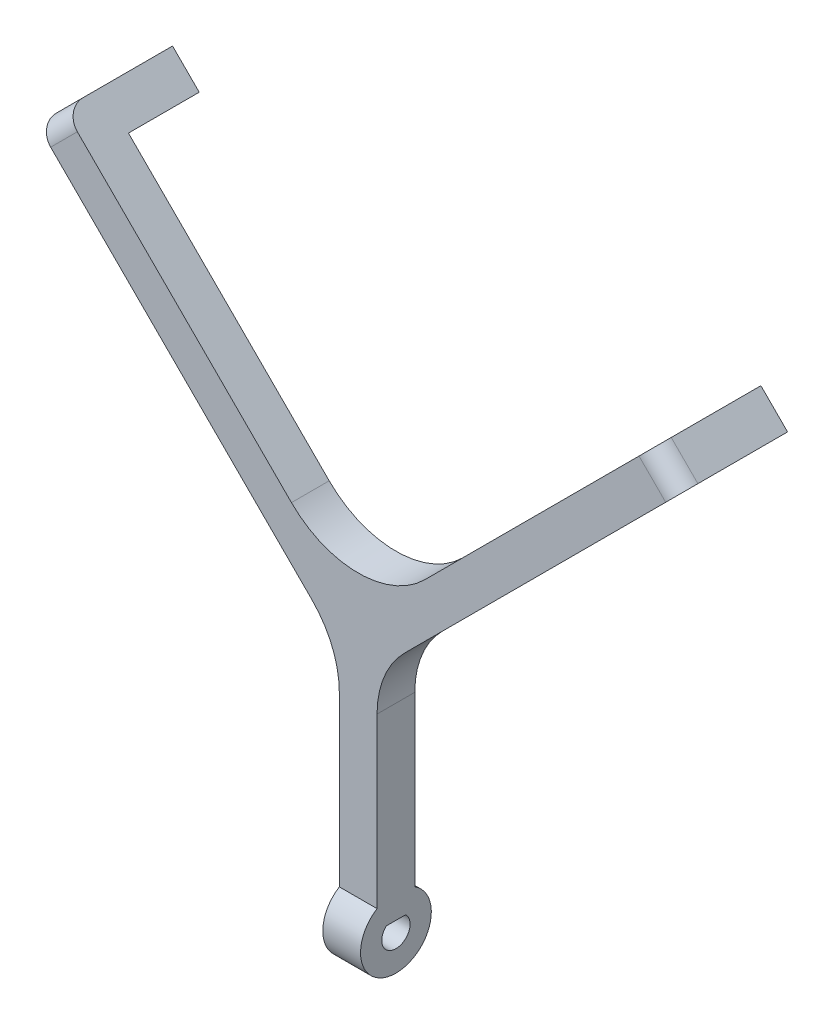
SolidWorks part; units mm, degrees
material "PLA"
ref_plane "Plan de face" through (0, 0, 0) normal (0, 0, 1) x (1, 0, 0)
ref_plane "Plan de dessus" through (0, 0, 0) normal (0, 1, 0) x (1, 0, 0)
ref_plane "Plan de droite" through (0, 0, 0) normal (1, 0, 0) x (0, 0, -1)
sketch "Esquisse1" plane through (0, 0, 0) normal (0, 0, 1) x (1, 0, 0)
  line L1 (0, 0) -> (136, 0) construction
  line L2 (0, 0) -> (0, 120) construction
  line L3 (0, 120) -> (136, 120) construction
  line L4 (136, 0) -> (136, 120) construction
  line L16 (64, 0) -> (64, 50.3431)
  line L17 (64, 50.3431) -> (0, 114.3431)
  line L18 (0, 114.3431) -> (5.6569, 120)
  line L19 (5.6569, 120) -> (68, 57.6569)
  line L20 (68, 57.6569) -> (130.3431, 120)
  line L21 (130.3431, 120) -> (136, 114.3431)
  line L22 (136, 114.3431) -> (72, 50.3431)
  line L23 (72, 50.3431) -> (72, 0)
  line L24 (72, 0) -> (64, 0)
  point P19 (68, 0)
  dimension "D1" = 136
  dimension "D2" = 120
  dimension "D3" = 8
  dimension "D4" = 68
  dimension "D5" = 135
  dimension "D6" = 135
  dimension "D7" = 90
  dimension "D8" = 8
  dimension "D9" = 8
  dimension "D10" = 68
extrude "Boss.-Extru.1" add sketch "Esquisse1" along normal blind 8
sketch "Esquisse2" plane through (0, 0, 0) normal (0, 0, -1) x (-1, 0, 0)
  line L0 (-72, 50.3431) -> (-136, 114.3431) construction
  line L1 (-136, 114.3431) -> (-130.3431, 120) construction
  line L2 (-130.3431, 120) -> (-68, 57.6569) construction
  line L3 (-130.3431, 108.6863) -> (-136, 114.3431)
  line L4 (-136, 114.3431) -> (-130.3431, 120)
  line L5 (-130.3431, 120) -> (-124.6863, 114.3431)
  line L6 (-130.3431, 108.6863) -> (-124.6863, 114.3431)
  line L7 (0, 114.3431) -> (-64, 50.3431) construction
  line L8 (-68, 57.6569) -> (-5.6569, 120) construction
  line L9 (-5.6569, 120) -> (0, 114.3431) construction
  line L10 (0, 114.3431) -> (-5.6569, 108.6863)
  line L11 (-11.3137, 114.3431) -> (-5.6569, 120)
  line L12 (-5.6569, 120) -> (0, 114.3431)
  line L13 (-11.3137, 114.3431) -> (-5.6569, 108.6863)
  dimension "D1" = 8
  dimension "D2" = 8
extrude "Boss.-Extru.2" add sketch "Esquisse2" along normal blind 15
fillet "Congé1" radius 20 3 edges at (72, 50.3431, 4) (64, 50.3431, 4) (68, 57.6569, 4)
fillet "Congé2" radius 4 2 edges at (133.1716, 117.1716, 8) (2.8284, 117.1716, 8)
sketch "Esquisse3" plane through (64, 0, 0) normal (-1, 0, 0) x (0, 0, 1)
  line L0 (4, 0) -> (4, 33.6289) construction
  line L1 (8, 0) -> (0, 0) construction
  circle A0 centre (4, 0) radius 7.5
  dimension "D1" = 15
extrude "Boss.-Extru.3" add sketch "Esquisse3" against normal up to surface (8 mm away) up to face at (72, 21.0294, 4)
sketch "Esquisse4" plane through (64, 0, 0) normal (-1, 0, 0) x (0, 0, 1)
  line L7 (4, 0) -> (4, 7.4852) construction
  line L11 (1.9604, 2.2) -> (6.0396, 2.2)
  line L12 (0.3981, -3) -> (8.2082, -3) construction
  arc A1 (1.9604, 2.2) -> (6.0396, 2.2) centre (4, 0) ccw
  point P10 (4, 6)
  point P11 (4, 6)
  dimension "D1" = 6
  dimension "D2" = 5.2
extrude "Enlèv. mat.-Extru.1" cut sketch "Esquisse4" against normal through all
equation "\"long_tot\"= 120"
equation "\"espac_sub_arms\"= 120"
equation "\"épaiss_cadre\"= 8"
equation "\"long_protub\"= 15"
equation "\"rayon_conge\"= 3"
equation "\"diam_axe\"= 5"
equation "\"D1@Esquisse1\"=\"espac_sub_arms\"+\"épaiss_cadre\"*2"
equation "\"D2@Esquisse1\"=\"long_tot\""
equation "\"D3@Esquisse1\"=\"épaiss_cadre\""
equation "\"D4@Esquisse1\"=\"D1@Esquisse1\"/2"
equation "\"D6@Esquisse1\"=\"D5@Esquisse1\""
equation "\"D8@Esquisse1\"=\"épaiss_cadre\""
equation "\"D9@Esquisse1\"=\"épaiss_cadre\""
equation "\"D10@Esquisse1\"=\"D4@Esquisse1\""
equation "\"D1@Boss.-Extru.1\"=\"épaiss_cadre\""
equation "\"D1@Esquisse2\"=\"épaiss_cadre\""
equation "\"D2@Esquisse2\"=\"épaiss_cadre\""
equation "\"D1@Boss.-Extru.2\"=\"long_protub\""
